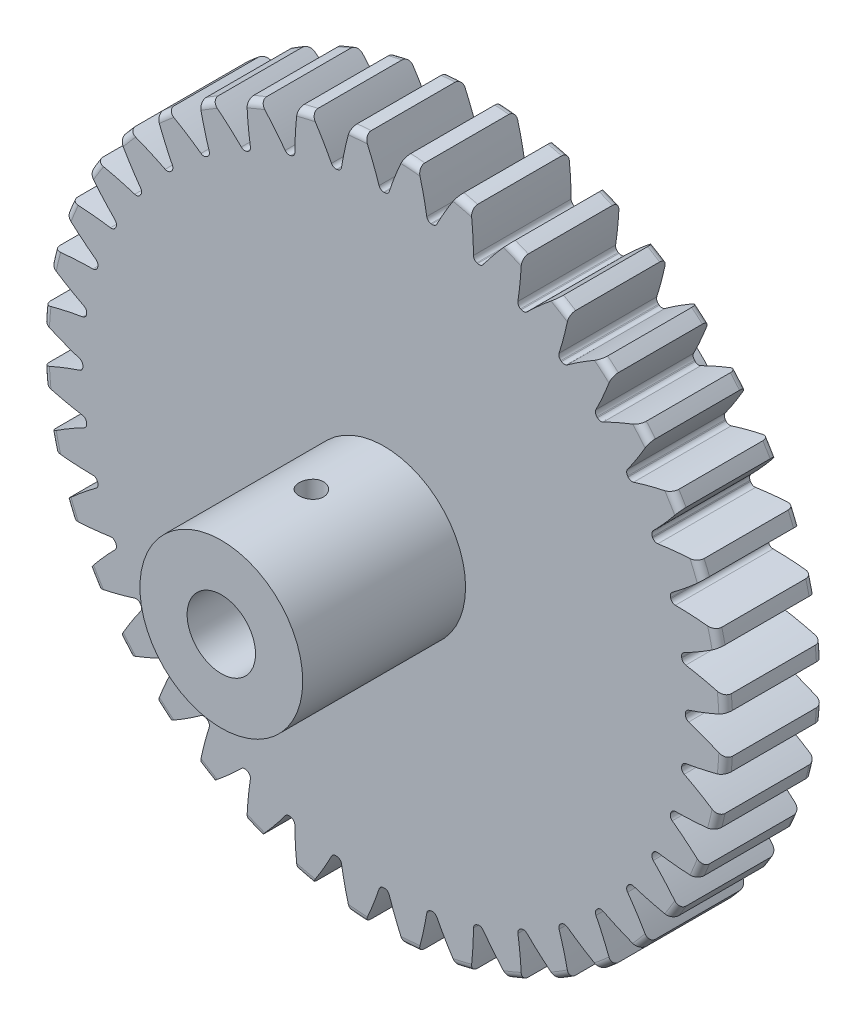
SolidWorks part; units mm, degrees
ref_plane "Front Plane" through (0, 0, 0) normal (0, 0, 1) x (1, 0, 0)
ref_plane "Top Plane" through (0, 0, 0) normal (0, 1, 0) x (1, 0, 0)
ref_plane "Right Plane" through (0, 0, 0) normal (1, 0, 0) x (0, 0, -1)
sketch "Sketch1" plane through (0, 0, 0) normal (0, 0, 1) x (1, 0, 0)
  line L0 (-508, 0) -> (508, 0) construction
  circle A0 centre (0, 0) radius 21 construction
  circle A1 centre (0, 0) radius 20 construction
  circle A2 centre (0, 0) radius 18.5 construction
  circle A3 centre (0, 0) radius 8 construction
  circle A4 centre (0, 0) radius 4 construction
  dimension "D2" = 1
  dimension "D3" = 2.5
  dimension "D1" = 2.5
sketch "Sketch2" plane through (0, 0, 0) normal (1, 0, 0) x (0, 0, -1)
  line L0 (0, 0) -> (-6, 0) construction
  line L1 (-6, 0) -> (-12, 0) construction
  dimension "Overall Width" = 12
  dimension "Face Width" = 6
sketch "Sketch4" plane through (0, 0, 0) normal (1, 0, 0) x (0, 0, -1)
  line L0 (-12, 4) -> (-12, 8)
  line L1 (-12, 8) -> (-6, 8)
  line L2 (-6, 8) -> (-6, 21)
  line L3 (-6, 21) -> (0, 21)
  line L4 (0, 21) -> (0, 4)
  line L5 (-6, 8) -> (-6, 0) construction
  line L6 (0, 21) -> (0, -21) construction
  line L7 (-6, 8) -> (0, 8) construction
  line L12 (-12, 4) -> (0, 4)
revolve "Revolve1" add sketch "Sketch4" angle 360 about L1
fillet "Fillet2" radius 0.42 4 edges at (0, 8, 12) (0, 8, 6) (0, 21, 6) (0, 21, 0)
sketch "Sketch7" plane through (0, 0, 6) normal (0, 0, 1) x (1, 0, 0)
  line L0 (0, 0) -> (0, 21) construction
  line L1 (0.7852, 19.9846) -> (1.1869, 20.9664) construction
  line L3 (1.6476, 20.9353) -> (1.5692, 19.9383) construction
  line L4 (1.5692, 19.9383) -> (1.4515, 18.443) construction
  line L5 (0, 0) -> (1.4515, 18.443) construction
  line L6 (0.7852, 19.9846) -> (0, 0) construction
  line L7 (0.7852, 19.9846) -> (0.8245, 20.9838) construction
  line L8 (0.7852, 19.9846) -> (0, 0) construction
  circle A0 centre (0, 0) radius 21 construction
  arc A1 (-0.027, 18.5) -> (0.027, 18.5) centre (0, 0) cw
  circle A2 centre (0, 0) radius 18.5 construction
  arc A3 (-0.7852, 19.9846) -> (0.7852, 19.9846) centre (0, 0) cw construction
  circle A4 centre (0, 0) radius 20 construction
  arc A5 (2.0774, 20.897) -> (1.2172, 20.9647) centre (0, 0) ccw construction
  arc A6 (0.7852, 19.9846) -> (2.3507, 19.8614) centre (0, 0) cw construction
  arc A7 (-1.2172, 20.9647) -> (1.2172, 20.9647) centre (0, 0) cw
  arc A8 (0.3122, 18.7056) -> (1.2172, 20.9647) centre (19.296, 12.4116) cw
  arc A9 (-0.3122, 18.7056) -> (-1.2172, 20.9647) centre (-19.296, 12.4116) ccw
  arc A10 (-0.027, 18.5) -> (-0.3122, 18.7056) centre (-0.0274, 18.8) cw
  arc A11 (0.027, 18.5) -> (0.3122, 18.7056) centre (0.0274, 18.8) ccw
  point P26 (-0.2447, 18.4984)
  point P29 (0.2447, 18.4984)
  dimension "D4" = 0.3
  dimension "D5" = 20
  dimension "D3" = 20
  dimension "D1" = 3.1416
  dimension "D2" = 1.5708
extrude "Cut-Extrude2" cut sketch "Sketch7" against normal through all
pattern_circular "CirPattern1" count 40 over 360 about axis through (0, 0, 12) along (0, 0, -1) of "Cut-Extrude2"
sketch "Sketch9" plane through (0, 0, 6) normal (0, 0, 1) x (1, 0, 0)
  circle A0 centre (0, 0) radius 8.42
  circle A1 centre (0, 0) radius 2.1
  circle A2 centre (0, 0) radius 5
  dimension "D1" = 16.84
  dimension "D2" = 4.2
  dimension "D3" = 10
extrude "Cut-Extrude3" cut sketch "Sketch9" along normal up to next contours A0 A2 region at (-8.1818, 0, 6)
extrude "Boss-Extrude1" add sketch "Sketch9<2>" against normal up to surface (6 mm away) contours A0 A2 | A2 A1 region at (-8.1818, 0, 6) region at (-4.8586, 0, 6) up to face at (0, 0, 0)
sketch "Sketch9<2>" plane through (0, 0, 6) normal (0, 0, 1) x (1, 0, 0) same geometry as "Sketch9"
extrude "Boss-Extrude2" add sketch "Sketch9<4>" along normal blind 10 and the other way blind 16 contours A2 A1 region at (-4.8586, 0, 6)
sketch "Sketch9<4>" plane through (0, 0, 6) normal (0, 0, 1) x (1, 0, 0) same geometry as "Sketch9"
ref_plane "Plane1" through (0, 5, 0) normal (0, 1, 0) x (1, 0, 0)
sketch "Sketch11" plane through (0, 5, 0) normal (0, 1, 0) x (1, 0, 0)
  line L0 (0.027, 0) -> (0.027, -6) construction
  line L1 (0.027, 4.5) -> (0.027, -10.5) construction
  circle A0 centre (0.027, 4.5) radius 0.75
  circle A1 centre (0.027, -10.5) radius 0.75
  point P4 (0.027, -3)
  point P5 (0.027, -3)
  dimension "D2" = 1.5
  dimension "D1" = 15
extrude "Cut-Extrude4" cut sketch "Sketch11" against normal through all contours A1 | A0 region at (0.027, 5, 10.5)
equation "\"D1@Sketch1\"=2.5*(\"Pitch Dia.@Sketch1\"/\"Number of Teeth@Sketch1\")"
equation "\"D1@CirPattern1\"=\"Number of Teeth@Sketch1\""
equation "\"D1@Fillet2\"=\"OD@Sketch1\"*.01"
equation "\"D1@Sketch7\"=3.14159*(\"Pitch Dia.@Sketch1\"/\"Number of Teeth@Sketch1\")"
equation "\"D2@Sketch7\"=\"D1@Sketch7\"/2"
equation "\"D4@Sketch7\"=\"D1@Sketch7\"*.0955"
equation "\"D5@Sketch7\"=\"Pitch Dia.@Sketch1\"/2"
